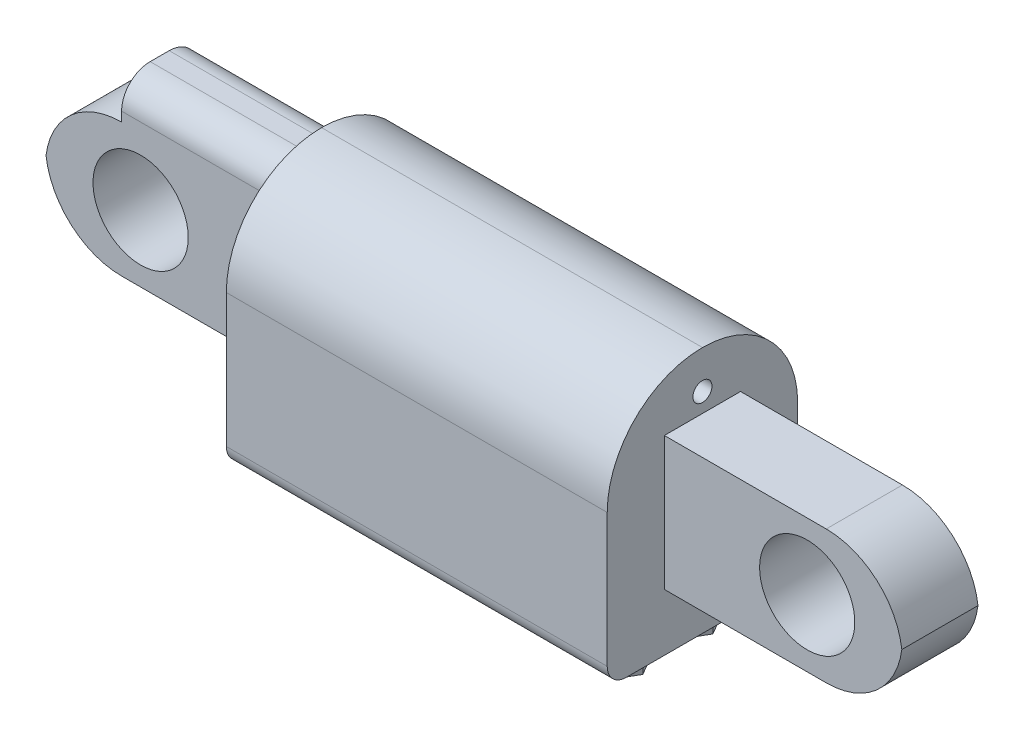
SolidWorks part; units mm, degrees
material "PLA"
ref_plane "Front" through (0, 0, 0) normal (0, 0, 1) x (1, 0, 0)
ref_plane "Top" through (0, 0, 0) normal (0, 1, 0) x (1, 0, 0)
ref_plane "Right" through (0, 0, 0) normal (1, 0, 0) x (0, 0, -1)
sketch "Sketch1" plane through (0, 0, 0) normal (0, 0, 1) x (1, 0, 0)
  line L1 (-6.35, 4.445) -> (9.525, 4.445)
  line L2 (-6.35, 4.445) -> (-6.35, -4.445)
  line L3 (-6.35, -4.445) -> (9.525, -4.445)
  line L4 (9.525, 4.445) -> (9.525, -4.445)
  circle A0 centre (0, 0) radius 3.175
  dimension "D1" = 6.35
  dimension "D2" = 6.35
  dimension "D3" = 4.445
  dimension "D4" = 4.445
  dimension "D5" = 15.875
extrude "Boss-Extrude1" add sketch "Sketch1" along normal blind 5.08
fillet "Fillet1" radius 5.08 2 edges at (-6.35, -4.445, 2.54) (-6.35, 4.445, 2.54)
sketch "Sketch2" plane through (9.525, 0, 0) normal (1, 0, 0) x (0, 0, -1)
  line L0 (-8.89, -8.255) -> (3.81, -8.255)
  line L1 (3.81, -8.255) -> (3.81, 8.255)
  line L2 (3.81, 8.255) -> (-8.89, 8.255)
  line L3 (-8.89, 8.255) -> (-8.89, -8.255)
  line L4 (0, -4.445) -> (0, 4.445)
  line L5 (0, 4.445) -> (-5.08, 4.445)
  line L6 (-5.08, 4.445) -> (-5.08, -4.445)
  line L7 (-5.08, -4.445) -> (0, -4.445)
  line L8 (0, -4.445) -> (0, 4.445)
  line L9 (0, 4.445) -> (-5.08, 4.445)
  line L10 (-5.08, 4.445) -> (-5.08, -4.445)
  line L11 (-5.08, -4.445) -> (0, -4.445)
  line M5 (0, -4.445) -> (0, 4.445)
  line M6 (0, 4.445) -> (-5.08, 4.445)
  line M7 (-5.08, 4.445) -> (-5.08, -4.445)
  line M8 (-5.08, -4.445) -> (0, -4.445)
  dimension "D1" = 0
  dimension "D2" = 3.81
extrude "Boss-Extrude2" add sketch "Sketch2" along normal blind 25.4 separate body contours L2 L3 L0 L1 M5 M8 M7 M6 | M8 M5 M6 M7 region at (9.525, 0, 8.6817) region at (9.525, 0, 2.54)
ref_plane "Plane1" through (22.225, 0, 0) normal (-1, 0, 0) x (0, 0, 1)
mirror "Mirror7" about plane through (22.225, 0, 0) normal (-1, 0, 0) of bodies 101
fillet "Fillet3" radius 6.35 2 edges at (22.225, 8.255, -3.81) (22.225, 8.255, 8.89)
sketch "Sketch3" plane through (0, 4.445, 0) normal (0, 1, 0) x (1, 0, 0)
  line L4 (9.525, 0) -> (-1.27, 0)
  line L5 (-1.27, 0) -> (-1.27, -5.08)
  line L6 (-1.27, -5.08) -> (9.525, -5.08)
  line L7 (9.525, -5.08) -> (9.525, 0)
  line L12 (9.525, 0) -> (-1.27, 0)
  line L13 (-1.27, 0) -> (-1.27, -5.08)
  line L14 (-1.27, -5.08) -> (9.525, -5.08)
  line L15 (9.525, -5.08) -> (9.525, 0)
  dimension "D1" = 0
extrude "Boss-Extrude3" add sketch "Sketch3" along normal blind 2.54
sketch "Sketch4" plane through (-1.27, 0, 0) normal (-1, 0, 0) x (0, 0, 1)
  line L8 (5.08, 6.985) -> (5.08, 4.445) construction
  line L9 (0, 4.445) -> (5.08, 4.445) construction
  circle A0 centre (2.54, 5.715) radius 0.635
  dimension "D1" = 1.27
  dimension "D2" = 1.27
  dimension "D3" = 2.54
extrude "Cut-Extrude1" cut sketch "Sketch4" against normal through all
fillet "Fillet6" radius 1.27 2 edges at (22.225, -8.255, -3.81) (22.225, -8.255, 8.89)
sketch "Sketch5" plane through (0, -8.255, 0) normal (0, -1, 0) x (1, 0, 0)
  line L0 (34.925, 1.905) -> (34.925, 3.175) construction
  line L1 (34.925, 7.62) -> (9.525, 7.62)
  line L2 (34.925, 7.62) -> (34.925, -2.54)
  line L3 (34.925, -2.54) -> (9.525, -2.54)
  line L4 (9.525, 7.62) -> (9.525, -2.54)
  line L5 (33.02, 5.4203) -> (34.29, 5.4203)
  line L6 (34.29, 5.4203) -> (34.925, 6.5201)
  line L7 (34.925, 6.5201) -> (34.29, 7.62)
  line L8 (34.29, 7.62) -> (33.02, 7.62)
  line L9 (33.02, 7.62) -> (32.385, 6.5201)
  line L10 (32.385, 6.5201) -> (33.02, 5.4203)
  line L11 (30.48, 5.4203) -> (31.75, 5.4203)
  line L12 (31.75, 5.4203) -> (32.385, 6.5201)
  line L13 (32.385, 6.5201) -> (31.75, 7.62)
  line L14 (31.75, 7.62) -> (30.48, 7.62)
  line L15 (30.48, 7.62) -> (29.845, 6.5201)
  line L16 (29.845, 6.5201) -> (30.48, 5.4203)
  line L17 (27.94, 5.4203) -> (29.21, 5.4203)
  line L18 (29.21, 5.4203) -> (29.845, 6.5201)
  line L19 (29.845, 6.5201) -> (29.21, 7.62)
  line L20 (29.21, 7.62) -> (27.94, 7.62)
  line L21 (27.94, 7.62) -> (27.305, 6.5201)
  line L22 (27.305, 6.5201) -> (27.94, 5.4203)
  line L23 (25.4, 5.4203) -> (26.67, 5.4203)
  line L24 (26.67, 5.4203) -> (27.305, 6.5201)
  line L25 (27.305, 6.5201) -> (26.67, 7.62)
  line L26 (26.67, 7.62) -> (25.4, 7.62)
  line L27 (25.4, 7.62) -> (24.765, 6.5201)
  line L28 (24.765, 6.5201) -> (25.4, 5.4203)
  line L29 (22.86, 5.4203) -> (24.13, 5.4203)
  line L30 (24.13, 5.4203) -> (24.765, 6.5201)
  line L31 (24.765, 6.5201) -> (24.13, 7.62)
  line L32 (24.13, 7.62) -> (22.86, 7.62)
  line L33 (22.86, 7.62) -> (22.225, 6.5201)
  line L34 (22.225, 6.5201) -> (22.86, 5.4203)
  line L35 (20.32, 5.4203) -> (21.59, 5.4203)
  line L36 (21.59, 5.4203) -> (22.225, 6.5201)
  line L37 (22.225, 6.5201) -> (21.59, 7.62)
  line L38 (21.59, 7.62) -> (20.32, 7.62)
  line L39 (20.32, 7.62) -> (19.685, 6.5201)
  line L40 (19.685, 6.5201) -> (20.32, 5.4203)
  line L41 (17.78, 5.4203) -> (19.05, 5.4203)
  line L42 (19.05, 5.4203) -> (19.685, 6.5201)
  line L43 (19.685, 6.5201) -> (19.05, 7.62)
  line L44 (19.05, 7.62) -> (17.78, 7.62)
  line L45 (17.78, 7.62) -> (17.145, 6.5201)
  line L46 (17.145, 6.5201) -> (17.78, 5.4203)
  line L47 (15.24, 5.4203) -> (16.51, 5.4203)
  line L48 (16.51, 5.4203) -> (17.145, 6.5201)
  line L49 (17.145, 6.5201) -> (16.51, 7.62)
  line L50 (16.51, 7.62) -> (15.24, 7.62)
  line L51 (15.24, 7.62) -> (14.605, 6.5201)
  line L52 (14.605, 6.5201) -> (15.24, 5.4203)
  line L53 (12.7, 5.4203) -> (13.97, 5.4203)
  line L54 (13.97, 5.4203) -> (14.605, 6.5201)
  line L55 (14.605, 6.5201) -> (13.97, 7.62)
  line L56 (13.97, 7.62) -> (12.7, 7.62)
  line L57 (12.7, 7.62) -> (12.065, 6.5201)
  line L58 (12.065, 6.5201) -> (12.7, 5.4203)
  line L59 (10.16, 5.4203) -> (11.43, 5.4203)
  line L60 (11.43, 5.4203) -> (12.065, 6.5201)
  line L61 (12.065, 6.5201) -> (11.43, 7.62)
  line L62 (11.43, 7.62) -> (10.16, 7.62)
  line L63 (10.16, 7.62) -> (9.525, 6.5201)
  line L64 (9.525, 6.5201) -> (10.16, 5.4203)
  line L65 (30.48, 3.0835) -> (31.75, 3.0835)
  line L66 (31.75, 3.0835) -> (32.385, 4.1833)
  line L67 (32.385, 4.1833) -> (31.75, 5.2832)
  line L68 (31.75, 5.2832) -> (30.48, 5.2832)
  line L69 (30.48, 5.2832) -> (29.845, 4.1833)
  line L70 (29.845, 4.1833) -> (30.48, 3.0835)
  line L71 (27.94, 3.0835) -> (29.21, 3.0835)
  line L72 (29.21, 3.0835) -> (29.845, 4.1833)
  line L73 (29.845, 4.1833) -> (29.21, 5.2832)
  line L74 (29.21, 5.2832) -> (27.94, 5.2832)
  line L75 (27.94, 5.2832) -> (27.305, 4.1833)
  line L76 (27.305, 4.1833) -> (27.94, 3.0835)
  line L77 (25.4, 3.0835) -> (26.67, 3.0835)
  line L78 (26.67, 3.0835) -> (27.305, 4.1833)
  line L79 (27.305, 4.1833) -> (26.67, 5.2832)
  line L80 (26.67, 5.2832) -> (25.4, 5.2832)
  line L81 (25.4, 5.2832) -> (24.765, 4.1833)
  line L82 (24.765, 4.1833) -> (25.4, 3.0835)
  line L83 (22.86, 3.0835) -> (24.13, 3.0835)
  line L84 (24.13, 3.0835) -> (24.765, 4.1833)
  line L85 (24.765, 4.1833) -> (24.13, 5.2832)
  line L86 (24.13, 5.2832) -> (22.86, 5.2832)
  line L87 (22.86, 5.2832) -> (22.225, 4.1833)
  line L88 (22.225, 4.1833) -> (22.86, 3.0835)
  line L89 (20.32, 3.0835) -> (21.59, 3.0835)
  line L90 (21.59, 3.0835) -> (22.225, 4.1833)
  line L91 (22.225, 4.1833) -> (21.59, 5.2832)
  line L92 (21.59, 5.2832) -> (20.32, 5.2832)
  line L93 (20.32, 5.2832) -> (19.685, 4.1833)
  line L94 (19.685, 4.1833) -> (20.32, 3.0835)
  line L95 (17.78, 3.0835) -> (19.05, 3.0835)
  line L96 (19.05, 3.0835) -> (19.685, 4.1833)
  line L97 (19.685, 4.1833) -> (19.05, 5.2832)
  line L98 (19.05, 5.2832) -> (17.78, 5.2832)
  line L99 (17.78, 5.2832) -> (17.145, 4.1833)
  line L100 (17.145, 4.1833) -> (17.78, 3.0835)
  line L101 (15.24, 3.0835) -> (16.51, 3.0835)
  line L102 (16.51, 3.0835) -> (17.145, 4.1833)
  line L103 (17.145, 4.1833) -> (16.51, 5.2832)
  line L104 (16.51, 5.2832) -> (15.24, 5.2832)
  line L105 (15.24, 5.2832) -> (14.605, 4.1833)
  line L106 (14.605, 4.1833) -> (15.24, 3.0835)
  line L107 (12.7, 3.0835) -> (13.97, 3.0835)
  line L108 (13.97, 3.0835) -> (14.605, 4.1833)
  line L109 (14.605, 4.1833) -> (13.97, 5.2832)
  line L110 (13.97, 5.2832) -> (12.7, 5.2832)
  line L111 (12.7, 5.2832) -> (12.065, 4.1833)
  line L112 (12.065, 4.1833) -> (12.7, 3.0835)
  line L113 (10.16, 3.0835) -> (11.43, 3.0835)
  line L114 (11.43, 3.0835) -> (12.065, 4.1833)
  line L115 (12.065, 4.1833) -> (11.43, 5.2832)
  line L116 (11.43, 5.2832) -> (10.16, 5.2832)
  line L117 (10.16, 5.2832) -> (9.525, 4.1833)
  line L118 (9.525, 4.1833) -> (10.16, 3.0835)
  line L119 (30.48, 0.7467) -> (31.75, 0.7467)
  line L120 (31.75, 0.7467) -> (32.385, 1.8465)
  line L121 (32.385, 1.8465) -> (31.75, 2.9464)
  line L122 (31.75, 2.9464) -> (30.48, 2.9464)
  line L123 (30.48, 2.9464) -> (29.845, 1.8465)
  line L124 (29.845, 1.8465) -> (30.48, 0.7467)
  line L125 (27.94, 0.7467) -> (29.21, 0.7467)
  line L126 (29.21, 0.7467) -> (29.845, 1.8465)
  line L127 (29.845, 1.8465) -> (29.21, 2.9464)
  line L128 (29.21, 2.9464) -> (27.94, 2.9464)
  line L129 (27.94, 2.9464) -> (27.305, 1.8465)
  line L130 (27.305, 1.8465) -> (27.94, 0.7467)
  line L131 (25.4, 0.7467) -> (26.67, 0.7467)
  line L132 (26.67, 0.7467) -> (27.305, 1.8465)
  line L133 (27.305, 1.8465) -> (26.67, 2.9464)
  line L134 (26.67, 2.9464) -> (25.4, 2.9464)
  line L135 (25.4, 2.9464) -> (24.765, 1.8465)
  line L136 (24.765, 1.8465) -> (25.4, 0.7467)
  line L137 (22.86, 0.7467) -> (24.13, 0.7467)
  line L138 (24.13, 0.7467) -> (24.765, 1.8465)
  line L139 (24.765, 1.8465) -> (24.13, 2.9464)
  line L140 (24.13, 2.9464) -> (22.86, 2.9464)
  line L141 (22.86, 2.9464) -> (22.225, 1.8465)
  line L142 (22.225, 1.8465) -> (22.86, 0.7467)
  line L143 (20.32, 0.7467) -> (21.59, 0.7467)
  line L144 (21.59, 0.7467) -> (22.225, 1.8465)
  line L145 (22.225, 1.8465) -> (21.59, 2.9464)
  line L146 (21.59, 2.9464) -> (20.32, 2.9464)
  line L147 (20.32, 2.9464) -> (19.685, 1.8465)
  line L148 (19.685, 1.8465) -> (20.32, 0.7467)
  line L149 (17.78, 0.7467) -> (19.05, 0.7467)
  line L150 (19.05, 0.7467) -> (19.685, 1.8465)
  line L151 (19.685, 1.8465) -> (19.05, 2.9464)
  line L152 (19.05, 2.9464) -> (17.78, 2.9464)
  line L153 (17.78, 2.9464) -> (17.145, 1.8465)
  line L154 (17.145, 1.8465) -> (17.78, 0.7467)
  line L155 (15.24, 0.7467) -> (16.51, 0.7467)
  line L156 (16.51, 0.7467) -> (17.145, 1.8465)
  line L157 (17.145, 1.8465) -> (16.51, 2.9464)
  line L158 (16.51, 2.9464) -> (15.24, 2.9464)
  line L159 (15.24, 2.9464) -> (14.605, 1.8465)
  line L160 (14.605, 1.8465) -> (15.24, 0.7467)
  line L161 (12.7, 0.7467) -> (13.97, 0.7467)
  line L162 (13.97, 0.7467) -> (14.605, 1.8465)
  line L163 (14.605, 1.8465) -> (13.97, 2.9464)
  line L164 (13.97, 2.9464) -> (12.7, 2.9464)
  line L165 (12.7, 2.9464) -> (12.065, 1.8465)
  line L166 (12.065, 1.8465) -> (12.7, 0.7467)
  line L167 (10.16, 0.7467) -> (11.43, 0.7467)
  line L168 (11.43, 0.7467) -> (12.065, 1.8465)
  line L169 (12.065, 1.8465) -> (11.43, 2.9464)
  line L170 (11.43, 2.9464) -> (10.16, 2.9464)
  line L171 (10.16, 2.9464) -> (9.525, 1.8465)
  line L172 (9.525, 1.8465) -> (10.16, 0.7467)
  line L173 (30.48, -1.5901) -> (31.75, -1.5901)
  line L174 (31.75, -1.5901) -> (32.385, -0.4903)
  line L175 (32.385, -0.4903) -> (31.75, 0.6096)
  line L176 (31.75, 0.6096) -> (30.48, 0.6096)
  line L177 (30.48, 0.6096) -> (29.845, -0.4903)
  line L178 (29.845, -0.4903) -> (30.48, -1.5901)
  line L179 (27.94, -1.5901) -> (29.21, -1.5901)
  line L180 (29.21, -1.5901) -> (29.845, -0.4903)
  line L181 (29.845, -0.4903) -> (29.21, 0.6096)
  line L182 (29.21, 0.6096) -> (27.94, 0.6096)
  line L183 (27.94, 0.6096) -> (27.305, -0.4903)
  line L184 (27.305, -0.4903) -> (27.94, -1.5901)
  line L185 (25.4, -1.5901) -> (26.67, -1.5901)
  line L186 (26.67, -1.5901) -> (27.305, -0.4903)
  line L187 (27.305, -0.4903) -> (26.67, 0.6096)
  line L188 (26.67, 0.6096) -> (25.4, 0.6096)
  line L189 (25.4, 0.6096) -> (24.765, -0.4903)
  line L190 (24.765, -0.4903) -> (25.4, -1.5901)
  line L191 (22.86, -1.5901) -> (24.13, -1.5901)
  line L192 (24.13, -1.5901) -> (24.765, -0.4903)
  line L193 (24.765, -0.4903) -> (24.13, 0.6096)
  line L194 (24.13, 0.6096) -> (22.86, 0.6096)
  line L195 (22.86, 0.6096) -> (22.225, -0.4903)
  line L196 (22.225, -0.4903) -> (22.86, -1.5901)
  line L197 (20.32, -1.5901) -> (21.59, -1.5901)
  line L198 (21.59, -1.5901) -> (22.225, -0.4903)
  line L199 (22.225, -0.4903) -> (21.59, 0.6096)
  line L200 (21.59, 0.6096) -> (20.32, 0.6096)
  line L201 (20.32, 0.6096) -> (19.685, -0.4903)
  line L202 (19.685, -0.4903) -> (20.32, -1.5901)
  line L203 (17.78, -1.5901) -> (19.05, -1.5901)
  line L204 (19.05, -1.5901) -> (19.685, -0.4903)
  line L205 (19.685, -0.4903) -> (19.05, 0.6096)
  line L206 (19.05, 0.6096) -> (17.78, 0.6096)
  line L207 (17.78, 0.6096) -> (17.145, -0.4903)
  line L208 (17.145, -0.4903) -> (17.78, -1.5901)
  line L209 (15.24, -1.5901) -> (16.51, -1.5901)
  line L210 (16.51, -1.5901) -> (17.145, -0.4903)
  line L211 (17.145, -0.4903) -> (16.51, 0.6096)
  line L212 (16.51, 0.6096) -> (15.24, 0.6096)
  line L213 (15.24, 0.6096) -> (14.605, -0.4903)
  line L214 (14.605, -0.4903) -> (15.24, -1.5901)
  line L215 (12.7, -1.5901) -> (13.97, -1.5901)
  line L216 (13.97, -1.5901) -> (14.605, -0.4903)
  line L217 (14.605, -0.4903) -> (13.97, 0.6096)
  line L218 (13.97, 0.6096) -> (12.7, 0.6096)
  line L219 (12.7, 0.6096) -> (12.065, -0.4903)
  line L220 (12.065, -0.4903) -> (12.7, -1.5901)
  line L221 (10.16, -1.5901) -> (11.43, -1.5901)
  line L222 (11.43, -1.5901) -> (12.065, -0.4903)
  line L223 (12.065, -0.4903) -> (11.43, 0.6096)
  line L224 (11.43, 0.6096) -> (10.16, 0.6096)
  line L225 (10.16, 0.6096) -> (9.525, -0.4903)
  line L226 (9.525, -0.4903) -> (10.16, -1.5901)
  line L227 (30.48, -3.9269) -> (31.75, -3.9269)
  line L228 (31.75, -3.9269) -> (32.385, -2.8271)
  line L229 (32.385, -2.8271) -> (31.75, -1.7272)
  line L230 (31.75, -1.7272) -> (30.48, -1.7272)
  line L231 (30.48, -1.7272) -> (29.845, -2.8271)
  line L232 (29.845, -2.8271) -> (30.48, -3.9269)
  line L233 (27.94, -3.9269) -> (29.21, -3.9269)
  line L234 (29.21, -3.9269) -> (29.845, -2.8271)
  line L235 (29.845, -2.8271) -> (29.21, -1.7272)
  line L236 (29.21, -1.7272) -> (27.94, -1.7272)
  line L237 (27.94, -1.7272) -> (27.305, -2.8271)
  line L238 (27.305, -2.8271) -> (27.94, -3.9269)
  line L239 (25.4, -3.9269) -> (26.67, -3.9269)
  line L240 (26.67, -3.9269) -> (27.305, -2.8271)
  line L241 (27.305, -2.8271) -> (26.67, -1.7272)
  line L242 (26.67, -1.7272) -> (25.4, -1.7272)
  line L243 (25.4, -1.7272) -> (24.765, -2.8271)
  line L244 (24.765, -2.8271) -> (25.4, -3.9269)
  line L245 (22.86, -3.9269) -> (24.13, -3.9269)
  line L246 (24.13, -3.9269) -> (24.765, -2.8271)
  line L247 (24.765, -2.8271) -> (24.13, -1.7272)
  line L248 (24.13, -1.7272) -> (22.86, -1.7272)
  line L249 (22.86, -1.7272) -> (22.225, -2.8271)
  line L250 (22.225, -2.8271) -> (22.86, -3.9269)
  line L251 (20.32, -3.9269) -> (21.59, -3.9269)
  line L252 (21.59, -3.9269) -> (22.225, -2.8271)
  line L253 (22.225, -2.8271) -> (21.59, -1.7272)
  line L254 (21.59, -1.7272) -> (20.32, -1.7272)
  line L255 (20.32, -1.7272) -> (19.685, -2.8271)
  line L256 (19.685, -2.8271) -> (20.32, -3.9269)
  line L257 (17.78, -3.9269) -> (19.05, -3.9269)
  line L258 (19.05, -3.9269) -> (19.685, -2.8271)
  line L259 (19.685, -2.8271) -> (19.05, -1.7272)
  line L260 (19.05, -1.7272) -> (17.78, -1.7272)
  line L261 (17.78, -1.7272) -> (17.145, -2.8271)
  line L262 (17.145, -2.8271) -> (17.78, -3.9269)
  line L263 (15.24, -3.9269) -> (16.51, -3.9269)
  line L264 (16.51, -3.9269) -> (17.145, -2.8271)
  line L265 (17.145, -2.8271) -> (16.51, -1.7272)
  line L266 (16.51, -1.7272) -> (15.24, -1.7272)
  line L267 (15.24, -1.7272) -> (14.605, -2.8271)
  line L268 (14.605, -2.8271) -> (15.24, -3.9269)
  line L269 (12.7, -3.9269) -> (13.97, -3.9269)
  line L270 (13.97, -3.9269) -> (14.605, -2.8271)
  line L271 (14.605, -2.8271) -> (13.97, -1.7272)
  line L272 (13.97, -1.7272) -> (12.7, -1.7272)
  line L273 (12.7, -1.7272) -> (12.065, -2.8271)
  line L274 (12.065, -2.8271) -> (12.7, -3.9269)
  line L275 (10.16, -3.9269) -> (11.43, -3.9269)
  line L276 (11.43, -3.9269) -> (12.065, -2.8271)
  line L277 (12.065, -2.8271) -> (11.43, -1.7272)
  line L278 (11.43, -1.7272) -> (10.16, -1.7272)
  line L279 (10.16, -1.7272) -> (9.525, -2.8271)
  line L280 (9.525, -2.8271) -> (10.16, -3.9269)
  line L281 (33.02, 3.0835) -> (34.29, 3.0835)
  line L282 (34.29, 3.0835) -> (34.925, 4.1833)
  line L283 (34.925, 4.1833) -> (34.29, 5.2832)
  line L284 (34.29, 5.2832) -> (33.02, 5.2832)
  line L285 (33.02, 5.2832) -> (32.385, 4.1833)
  line L286 (32.385, 4.1833) -> (33.02, 3.0835)
  line L287 (33.02, 0.7467) -> (34.29, 0.7467)
  line L288 (34.29, 0.7467) -> (34.925, 1.8465)
  line L289 (34.925, 1.8465) -> (34.29, 2.9464)
  line L290 (34.29, 2.9464) -> (33.02, 2.9464)
  line L291 (33.02, 2.9464) -> (32.385, 1.8465)
  line L292 (32.385, 1.8465) -> (33.02, 0.7467)
  line L293 (33.02, -1.5901) -> (34.29, -1.5901)
  line L294 (34.29, -1.5901) -> (34.925, -0.4903)
  line L295 (34.925, -0.4903) -> (34.29, 0.6096)
  line L296 (34.29, 0.6096) -> (33.02, 0.6096)
  line L297 (33.02, 0.6096) -> (32.385, -0.4903)
  line L298 (32.385, -0.4903) -> (33.02, -1.5901)
  line L299 (33.02, -3.9269) -> (34.29, -3.9269)
  line L300 (34.29, -3.9269) -> (34.925, -2.8271)
  line L301 (34.925, -2.8271) -> (34.29, -1.7272)
  line L302 (34.29, -1.7272) -> (33.02, -1.7272)
  line L303 (33.02, -1.7272) -> (32.385, -2.8271)
  line L304 (32.385, -2.8271) -> (33.02, -3.9269)
  circle A0 centre (33.655, 6.5201) radius 1.0999 construction
  dimension "D1" = 2.54
  dimension "D2" = 10
  dimension "D3" = 5
extrude "Boss-Extrude7" add sketch "Sketch5" along normal blind 0.381 contours L9 L10 L5 L6 L7 L1 | L21 L22 L17 L18 L19 L1 | L33 L34 L29 L30 L31 L1 | L45 L46 L41 L42 L43 L1 | L57 L58 L53 L54 L55 L1 | L65 L66 L67 L68 L69 L70 | L77 L78 L79 L80 L81 L82 | L89 L90 L91 L92 L93 L94 | L101 L102 L103 L104 L105 L106 | L113 L114 L115 L116 L117 L118 | L287 L288 L289 L290 L291 L292 | L125 L126 L127 L128 L129 L130 | L137 L138 L139 L140 L141 L142 | L149 L150 L151 L152 L153 L154 | L161 L162 L163 L164 L165 L166 | L173 L174 L175 L176 L177 L178 | L185 L186 L187 L188 L189 L190 | L197 L198 L199 L200 L201 L202 | L209 L210 L211 L212 L213 L214 | L221 L222 L223 L224 L225 L226 region at (33.655, -8.255, 6.5201) region at (28.575, -8.255, 6.5201) region at (23.495, -8.255, 6.5201) region at (18.415, -8.255, 6.5201) region at (13.335, -8.255, 6.5201)
fillet "Fillet7" radius 1.905 2 edges at (4.1275, 6.985, 0) (4.1275, 6.985, 5.08)
